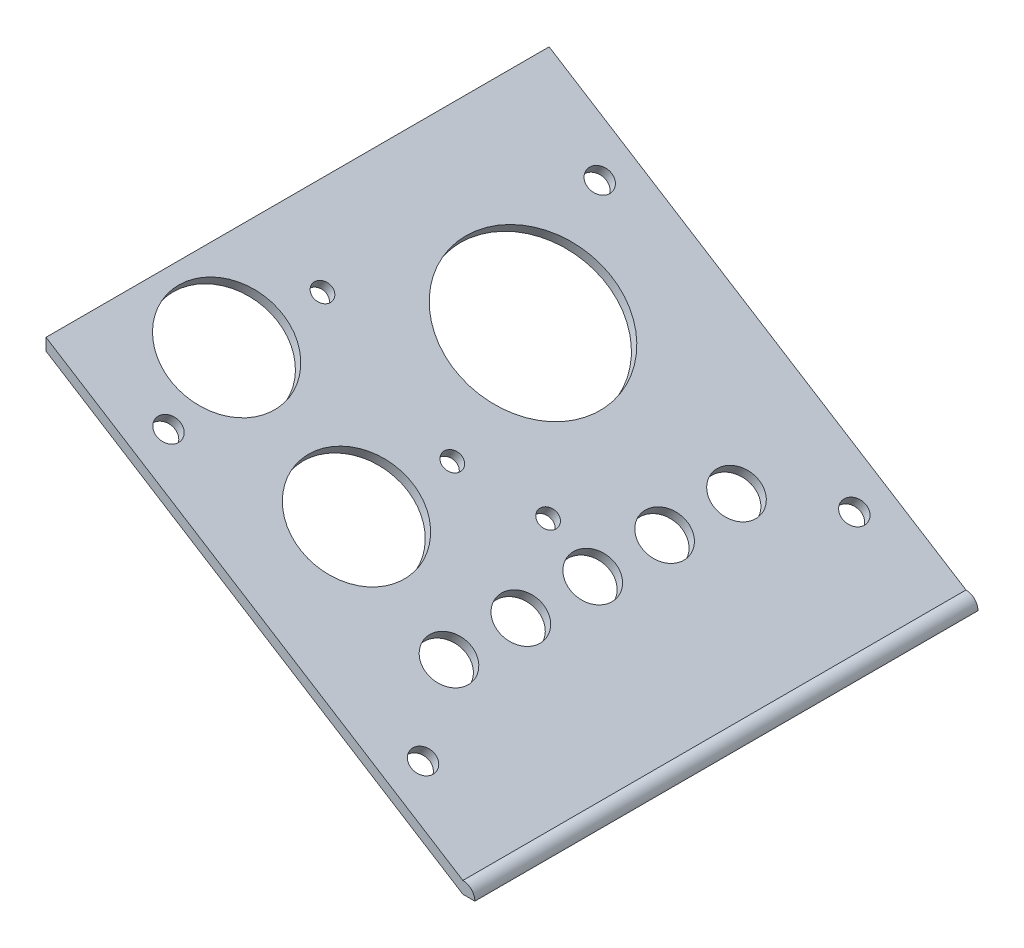
SolidWorks part; units mm, degrees
material "6061-T6 (SS)"
ref_plane "Front Plane" through (0, 0, 0) normal (0, 0, 1) x (1, 0, 0)
ref_plane "Top Plane" through (0, 0, 0) normal (0, 1, 0) x (1, 0, 0)
ref_plane "Right Plane" through (0, 0, 0) normal (1, 0, 0) x (0, 0, -1)
sketch "Sketch1" plane through (0, 0, 0) normal (0, 0, 1) x (1, 0, 0)
  line L2 (110.49, -69.425) -> (0, 0)
  line L3 (0, 0) -> (110.49, 0) construction
  line L4 (110.49, 0) -> (110.49, -66.25) construction
  line L11 (0, 0) -> (0, 3.175)
  line L12 (0, 3.175) -> (110.49, -66.25)
  line L16 (110.49, -66.25) -> (110.49, -69.425)
  dimension "D1" = 110.49
  dimension "D2" = 69.425
  dimension "D3" = 3.175
extrude "Boss-Extrude1" add sketch "Sketch1" along normal blind 133.35 contours L2 L11 L12 L16
sketch "Sketch2" plane through (1.4303, 2.2763, 0) normal (0.532, 0.8467, 0) x (0.8467, -0.532, 0)
  line L0 (-1.6892, 0) -> (128.8017, 0) construction
  line L1 (-1.6892, -133.35) -> (-1.6892, 0) construction
  circle A4 centre (42.7608, -41.91) radius 21
  point P0 (42.7608, -41.91)
  dimension "D8" = 42
  dimension "D1" = 41.91
  dimension "D9" = 44.45
extrude "Cut-Extrude1" cut sketch "Sketch2" against normal through all contours A4
sketch "Sketch3" plane through (110.49, 0, 0) normal (1, 0, 0) x (0, 0, -1)
  line L1 (-133.35, -66.25) -> (0, -66.25)
  line L2 (-133.35, -66.25) -> (-133.35, -69.425)
  line L3 (-133.35, -69.425) -> (0, -69.425)
  line L4 (0, -66.25) -> (0, -69.425)
extrude "Boss-Extrude2" add sketch "Sketch3" along normal blind 3.175
fillet "Fillet1" radius 3.175 1 edges at (113.665, -66.25, 66.675)
sketch "Sketch5" plane through (1.4303, 2.2763, 0) normal (0.532, 0.8467, 0) x (0.8467, -0.532, 0)
  line L4 (-1.6892, -66.675) -> (133.1792, -66.675) construction
  line L5 (-1.6892, -133.35) -> (-1.6892, 0) construction
  line L6 (133.1792, -133.35) -> (133.1792, 0) construction
  circle A0 centre (17.3608, -101.6) radius 15
  circle A1 centre (58.0008, -101.6) radius 15
  dimension "D1" = 30
  dimension "D2" = 19.05
  dimension "D3" = 30
  dimension "D4" = 59.69
  dimension "D5" = 0
sketch "Sketch6" plane through (1.4303, 2.2763, 0) normal (0.532, 0.8467, 0) x (0.8467, -0.532, 0)
  line L0 (-1.6892, -66.675) -> (128.8017, -66.675) construction
  line L1 (-1.6892, -133.35) -> (-1.6892, 0) construction
  line L2 (128.8017, -133.35) -> (128.8017, 0) construction
  line L3 (90.7017, -66.675) -> (90.7017, 0) construction
  line L6 (-1.6892, 0) -> (128.8017, 0) construction
  line L7 (90.7017, -66.675) -> (90.7017, -133.35) construction
  line L8 (-1.6892, -133.35) -> (128.8017, -133.35) construction
  circle A7 centre (90.7017, -66.675) radius 6.0325
  circle A8 centre (90.7017, -47.625) radius 6.0325
  circle A9 centre (90.7017, -28.575) radius 6.0325
  circle A10 centre (90.7017, -85.725) radius 6.0325
  circle A11 centre (90.7017, -104.775) radius 6.0325
  dimension "D1" = 12.065
  dimension "D2" = 38.1
  dimension "D3" = 3
  dimension "D4" = 3
extrude "Cut-Extrude2" cut sketch "Sketch5" against normal through all
extrude "Cut-Extrude3" cut sketch "Sketch6" against normal through all
sketch "Sketch7" plane through (0, 0, 0) normal (-0.532, -0.8467, 0) x (0.8467, -0.532, 0)
  line L0 (130.4909, 133.35) -> (0, 133.35) construction
  line L1 (130.4909, 133.35) -> (130.4909, 0) construction
  line L2 (0, 133.35) -> (0, 0) construction
  line L3 (0, 66.675) -> (133.1792, 66.675) construction
  line L4 (133.1792, 133.35) -> (133.1792, 0) construction
  circle A0 centre (105.0909, 123.825) radius 3.175
  circle A1 centre (25.4, 123.825) radius 3.175
  circle A2 centre (25.4, 9.525) radius 3.175
  circle A3 centre (105.0909, 9.525) radius 3.175
  dimension "D1" = 6.35
  dimension "D4" = 6.35
  dimension "D2" = 9.525
  dimension "D3" = 25.4
  dimension "D5" = 25.4
  dimension "D6" = 0
extrude "Cut-Extrude4" cut sketch "Sketch7" against normal through all
sketch "Sketch15" plane through (1.4303, 2.2763, 0) normal (0.532, 0.8467, 0) x (0.8467, -0.532, 0)
  line L0 (17.3608, -101.6) -> (17.3608, -76.2) construction
  line L1 (-1.6892, -66.675) -> (128.8017, -66.675) construction
  line L2 (-1.6892, -133.35) -> (-1.6892, 0) construction
  line L3 (128.8017, -133.35) -> (128.8017, 0) construction
  line L4 (90.7017, -60.6425) -> (90.7017, -72.7075) construction
  line L5 (58.0008, -101.6) -> (58.0008, -76.2) construction
  circle A0 centre (17.3608, -76.2) radius 2.5
  circle A2 centre (76.7317, -66.675) radius 2.5
  circle A3 centre (90.7017, -66.675) radius 6.0325 construction
  circle A4 centre (58.0008, -76.2) radius 2.5
  point P19 (90.7017, -66.675)
  dimension "D2" = 5
  dimension "D3" = 5
  dimension "D5" = 5
  dimension "D1" = 25.4
  dimension "D4" = 13.97
extrude "Cut-Extrude8" cut sketch "Sketch15" against normal through all
sketch "Sketch16" plane through (1.4303, 2.2763, 0) normal (0.532, 0.8467, 0) x (0.8467, -0.532, 0)
  line L0 (58.0008, -101.6) -> (40.018, -60.9694)
  line L1 (43.9459, -102.689) -> (52.5608, -59.2012) construction
  dimension "D1" = 35.079
  dimension "D2" = 44.4322
sketch "Sketch18" plane through (1.4303, 2.2763, 0) normal (0.532, 0.8467, 0) x (0.8467, -0.532, 0)
  circle A0 centre (42.7608, -41.91) radius 30.1625
  circle A1 centre (42.7608, -41.91) radius 21
  dimension "D1" = 60.325
extrude "Boss-Extrude3" add sketch "Sketch18" against normal up to surface (2.6884 mm away) up to face at (51.2276, -32.1882, 76.2)
